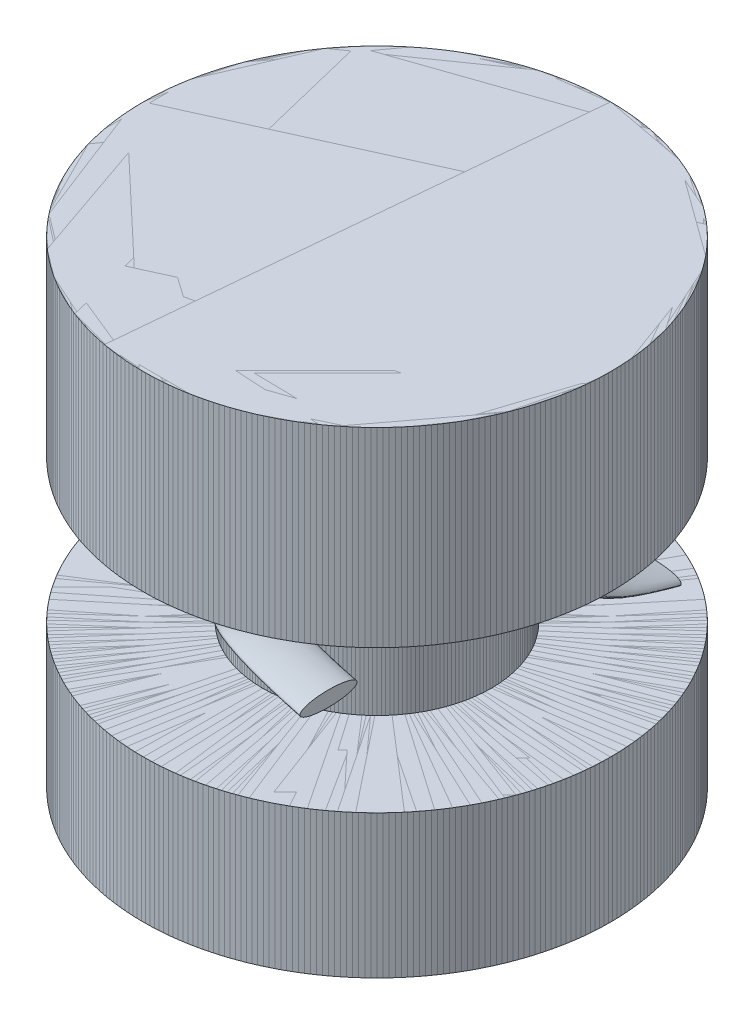
SolidWorks part; units mm, degrees
ref_plane "Front Plane" through (0, 0, 0) normal (0, 0, 1) x (1, 0, 0)
ref_plane "Top Plane" through (0, 0, 0) normal (0, 1, 0) x (1, 0, 0)
ref_plane "Right Plane" through (0, 0, 0) normal (1, 0, 0) x (0, 0, -1)
sketch "Sketch1" plane through (0, 0, 0) normal (0, 0, 1) x (1, 0, 0)
  line L0 (0, 0) -> (6.223, 0)
  line L1 (6.223, 0) -> (6.223, -5.08)
  line L2 (6.223, -5.08) -> (3.048, -5.08)
  line L3 (3.048, -5.08) -> (3.048, -8.89)
  line L4 (3.048, -8.89) -> (6.223, -8.89)
  line L5 (6.223, -8.89) -> (6.223, -12.7)
  line L6 (6.223, -12.7) -> (0, -12.7)
  line L7 (0, -12.7) -> (0, 0)
  dimension "D1" = 12.7
  dimension "D2" = 3.81
  dimension "D3" = 3.81
  dimension "D4" = 6.223
  dimension "D5" = 3.048
  dimension "D6" = 6.223
revolve "button body" add sketch "Sketch1" angle 360 about L7
ref_plane "spring path" through (4.318, 0, 0) normal (1, 0, 0) x (0, 0, -1)
sketch "Sketch2" plane through (4.318, 0, 0) normal (1, 0, 0) x (0, 0, -1)
  spline S0 degree 3 poles (2.9542, -4.563) (1.8538, -5.2739) (-1.4839, -5.7786) (3.0242, -6.9827) knots 0 0 0 0 1 1 1 1
ref_plane "spring cross section" through (0, 0, -3.0242) normal (0, 0, 1) x (1, 0, 0)
sketch "Sketch4" plane through (0, 0, -3.0242) normal (0, 0, 1) x (1, 0, 0)
  ellipse E0 centre (4.318, -6.9827) end of major axis (3.556, -6.9827) minor radius 0.2032
  dimension "D1" = 0
sweep "spring" add profiles "Sketch4" path "Sketch2"
ref_axis "center axis" through (0, 0, 0) along (0, -1, 0)
pattern_circular "moar springs" count 4 over 360 about axis through (0, 0, 0) along (0, -1, 0) of bodies 102
